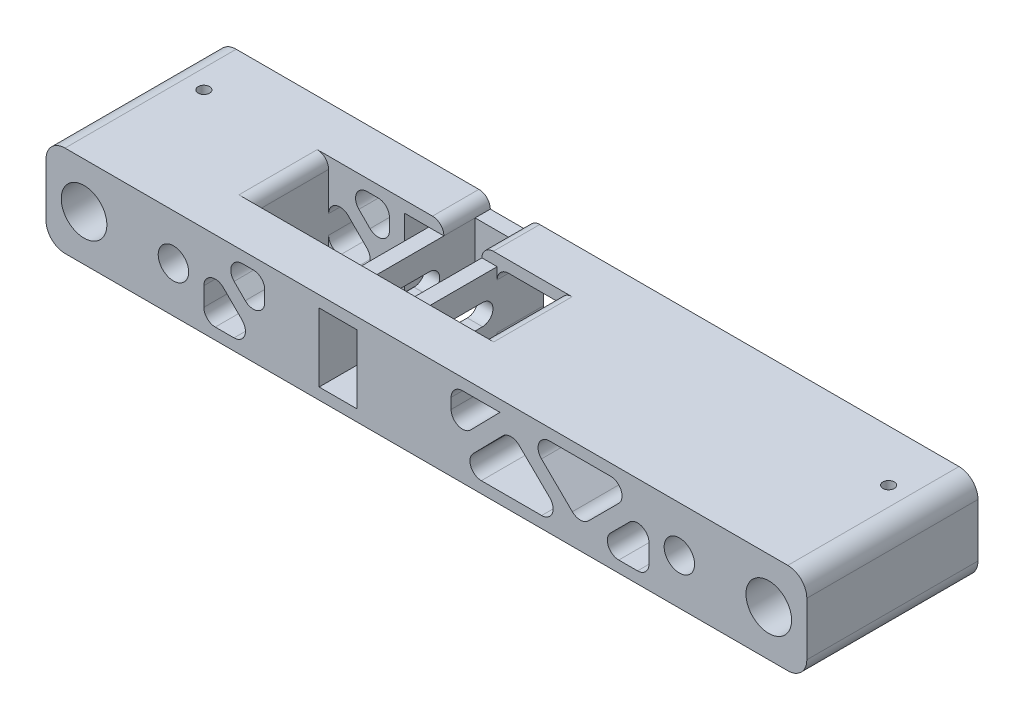
SolidWorks part; units mm, degrees
ref_plane "Front Plane" through (0, 0, 0) normal (0, 0, 1) x (1, 0, 0)
ref_plane "Top Plane" through (0, 0, 0) normal (0, 1, 0) x (1, 0, 0)
ref_plane "Right Plane" through (0, 0, 0) normal (1, 0, 0) x (0, 0, -1)
sketch "Sketch1" plane through (0, 0, 0) normal (0, 0, 1) x (1, 0, 0)
  line L0 (-58.5, 24) -> (-58.5, 0) construction
  line L1 (0, 0) -> (-100, 0)
  line L2 (0, 0) -> (0, 24)
  line L3 (0, 24) -> (-100, 24)
  line L4 (-100, 0) -> (-100, 24)
  circle A0 centre (-90, 12) radius 6
  circle A1 centre (-66.5, 12) radius 4
  point P9 (-100, 12)
  dimension "D3" = 12
  dimension "D4" = 8
  dimension "D1" = 100
  dimension "D2" = 24
  dimension "D5" = 23.5
  dimension "D6" = 10
  dimension "D7" = 8
  dimension "D8" = 41.5
extrude "Boss-Extrude1" add sketch "Sketch1" along normal blind 40
sketch "Sketch2" plane through (0, 0, 0) normal (0, 0, -1) x (-1, 0, 0)
  line L1 (100, 24) -> (0, 24)
  line L2 (100, 24) -> (100, 0)
  line L3 (100, 0) -> (0, 0)
  line L4 (0, 24) -> (0, 0)
extrude "Boss-Extrude2" add sketch "Sketch2" along normal blind 5
sketch "Sketch3" plane through (0, 24, 0) normal (0, 1, 0) x (1, 0, 0)
  line L0 (0, -40) -> (0, 5) construction
  line L1 (0, 5) -> (-58.5, 5)
  line L2 (0, 5) -> (0, -27.8)
  line L3 (0, -27.8) -> (-58.5, -27.8)
  line L4 (-58.5, 5) -> (-58.5, -27.8)
  line L5 (-100, -40) -> (-100, 5) construction
  line L7 (0, -40) -> (-100, -40) construction
  line L8 (-100, 5) -> (0, 5) construction
  dimension "D1" = 41.5
  dimension "D3" = 12.2
extrude "Cut-Extrude1" cut sketch "Sketch3" against normal up to next
mirror "Mirror2" of "Boss-Extrude2", "Cut-Extrude1", "Boss-Extrude1"
sketch "Sketch4" plane through (0, 0, 27.8) normal (0, 0, -1) x (-1, 0, 0)
  line L0 (58.5, 0) -> (58.5, 24) construction
  line L1 (28.2, 3) -> (18.2, 3)
  line L2 (28.2, 3) -> (28.2, 21)
  line L3 (28.2, 21) -> (18.2, 21)
  line L4 (18.2, 3) -> (18.2, 21)
  line L5 (28.2, 3) -> (18.2, 21) construction
  line L6 (28.2, 21) -> (18.2, 3) construction
  point P0 (23.2, 12)
  point P7 (58.5, 12)
  dimension "D1" = 30.3
  dimension "D2" = 10
  dimension "D3" = 18
extrude "Cut-Extrude2" cut sketch "Sketch4" against normal through all
sketch "Sketch5" plane through (0, 0, 27.8) normal (0, 0, -1) x (-1, 0, 0)
  line L0 (18.2, 3) -> (28.2, 3) construction
  line L1 (28.2, 21) -> (32.2, 21)
  line L2 (28.2, 21) -> (28.2, 3)
  line L3 (28.2, 3) -> (32.2, 3)
  line L4 (32.2, 21) -> (32.2, 3)
  line L5 (18.2, 21) -> (14.2, 21)
  line L6 (18.2, 21) -> (18.2, 3)
  line L7 (18.2, 3) -> (14.2, 3)
  line L8 (14.2, 21) -> (14.2, 3)
  dimension "D1" = 4
  dimension "D2" = 4
extrude "Boss-Extrude3" add sketch "Sketch5" along normal blind 28.8
sketch "Sketch6" plane through (0, 0, -1) normal (0, 0, -1) x (-1, 0, 0)
  line L1 (14.2, 21) -> (32.2, 21)
  line L2 (14.2, 21) -> (14.2, 3)
  line L3 (14.2, 3) -> (32.2, 3)
  line L4 (32.2, 21) -> (32.2, 3)
extrude "Boss-Extrude4" add sketch "Sketch6" along normal blind 4
sketch "Sketch7" plane through (-14.2, 0, 0) normal (1, 0, 0) x (0, 0, -1)
  line L0 (-20.05, 12) -> (-11.05, 12) construction
  line L1 (-20.05, 14.75) -> (-11.05, 14.75)
  line L2 (-20.05, 9.25) -> (-11.05, 9.25)
  line L3 (-27.8, 21) -> (-27.8, 3) construction
  line L4 (5, 21) -> (-27.8, 21) construction
  arc A0 (-20.05, 14.75) -> (-20.05, 9.25) centre (-20.05, 12) ccw
  arc A1 (-11.05, 9.25) -> (-11.05, 14.75) centre (-11.05, 12) ccw
  point P2 (-15.55, 12)
  point P7 (-22.8, 12)
  dimension "D1" = 9
  dimension "D2" = 5.5
  dimension "D3" = 5
  dimension "D4" = 9
extrude "Cut-Extrude3" cut sketch "Sketch7" against normal up to vertex
sketch "Sketch8" plane through (0, 21, 0) normal (0, 1, 0) x (1, 0, 0)
  line L0 (-32.2, 5) -> (-14.2, 5) construction
  line L1 (-18.2, 5) -> (58.5, 5)
  line L2 (-18.2, 5) -> (-18.2, -7.2)
  line L3 (-18.2, -7.2) -> (58.5, -7.2)
  line L4 (58.5, 5) -> (58.5, -7.2)
  line L5 (-58.5, 5) -> (-58.5, -27.8) construction
  line L6 (-28.2, 5) -> (-58.5, 5)
  line L7 (-28.2, 5) -> (-28.2, -7.2)
  line L8 (-28.2, -7.2) -> (-58.5, -7.2)
  line L9 (-58.5, 5) -> (-58.5, -7.2)
  line L10 (-28.2, 1) -> (-28.2, -27.8) construction
  line L11 (-18.2, 1) -> (-18.2, -27.8) construction
  line L12 (58.5, 5) -> (58.5, -27.8) construction
  dimension "D1" = 12.2
  dimension "D2" = 12.2
extrude "Boss-Extrude5" add sketch "Sketch8" along normal up to vertex (3 mm away)
sketch "Sketch13" plane through (58.5, 0, 0) normal (-1, 0, 0) x (0, 0, 1)
  line L0 (7.2, 24) -> (7.2, 21) construction
  line L1 (-5, 0) -> (7.2, 0)
  line L2 (-5, 0) -> (-5, 3)
  line L3 (-5, 3) -> (7.2, 3)
  line L4 (7.2, 0) -> (7.2, 3)
extrude "Boss-Extrude7" add sketch "Sketch13" along normal up to vertex
sketch "Sketch14" plane through (-58.5, 0, 0) normal (1, 0, 0) x (0, 0, -1)
  line L0 (-7.2, 24) -> (-7.2, 21) construction
  line L1 (5, 0) -> (-7.2, 0)
  line L2 (5, 0) -> (5, 3)
  line L3 (5, 3) -> (-7.2, 3)
  line L4 (-7.2, 0) -> (-7.2, 3)
extrude "Boss-Extrude8" add sketch "Sketch14" along normal up to vertex
sketch "Sketch9" plane through (0, 0, -5) normal (0, 0, -1) x (-1, 0, 0)
  line L0 (-58.5, 21) -> (-40.5, 3) construction
  line L2 (-40.5, 3) -> (-22.15, 21) construction
  line L3 (-58.5, 21) -> (14.2, 21) construction
  line L4 (-22.15, 21) -> (-4.4933, 3) construction
  line L5 (-4.4933, 3) -> (-4.4933, 21) construction
  line L6 (58.5, 21) -> (40.5, 3) construction
  line L8 (40.5, 3) -> (40.5, 21) construction
  line L9 (32.2, 21) -> (58.5, 21) construction
  line L10 (-58.5, 3) -> (-58.5, 21) construction
  line L11 (58.5, 0) -> (58.5, 24) construction
  line L12 (-58.5, 18.1716) -> (-43.3284, 3)
  line L13 (-37.6439, 3) -> (-22.1772, 18.1717)
  line L14 (-22.1772, 18.1717) -> (-7.2949, 3)
  line L15 (-2.4933, 3) -> (-2.4933, 21)
  line L16 (55.6716, 21) -> (42.5, 7.8284)
  line L17 (42.5, 7.8284) -> (42.5, 21)
  line L18 (-55.6716, 21) -> (-40.4864, 5.8149)
  line L19 (-40.4864, 5.8149) -> (-25.0061, 21)
  line L20 (-19.3484, 21) -> (-6.4933, 7.8949)
  line L21 (-6.4933, 7.8949) -> (-6.4933, 21)
  line L22 (58.5, 18.1716) -> (43.3284, 3)
  line L23 (38.5, 3) -> (38.5, 21)
  line L24 (-58.5, 18.1716) -> (-58.5, 21)
  line L25 (-58.5, 21) -> (-55.6716, 21)
  line L26 (-6.4933, 21) -> (-2.4933, 21)
  line L27 (-7.2949, 3) -> (-2.4933, 3)
  line L28 (-37.6439, 3) -> (-43.3284, 3)
  line L29 (-25.0061, 21) -> (-19.3484, 21)
  line L30 (-57.0858, 22.4142) -> (-40.4864, 5.8149) construction
  line L31 (-59.9142, 19.5858) -> (-40.5136, 0.1851) construction
  line L32 (-40.5136, 0.1851) -> (-22.1772, 18.1717) construction
  line L33 (-22.1772, 18.1717) -> (-2.4933, -1.8949) construction
  line L34 (-2.4933, -1.8949) -> (-2.4933, 21) construction
  line L35 (-22.1228, 23.8283) -> (-6.4933, 7.8949) construction
  line L36 (-40.4864, 5.8149) -> (-22.1228, 23.8283) construction
  line L37 (38.5, 21) -> (42.5, 21)
  line L38 (55.6716, 21) -> (58.5, 21)
  line L39 (58.5, 21) -> (58.5, 18.1716)
  line L40 (58.5, 3) -> (58.5, 21) construction
  line L41 (43.3284, 3) -> (38.5, 3)
  line L42 (38.5, -1.8284) -> (38.5, 21) construction
  line L43 (59.9142, 19.5858) -> (38.5, -1.8284) construction
  line L44 (57.0858, 22.4142) -> (42.5, 7.8284) construction
  line L45 (14.2, 3) -> (-58.5, 3) construction
  line L47 (32.2, 3) -> (58.5, 3) construction
  dimension "D1" = 45
  dimension "D2" = 45
  dimension "D3" = 2
  dimension "D4" = 2
extrude "Boss-Extrude6" add sketch "Sketch9" against normal up to vertex (12.2 mm away) up to point (-14.2, 21, 7.2)
sketch "Sketch11" plane through (0, 24, 0) normal (0, 1, 0) x (1, 0, 0)
  line L0 (96, 0) -> (84, 0) construction
  line L1 (-84, 0) -> (-96, 0) construction
  circle A0 centre (90, -8.5) radius 1.5
  circle A1 centre (-90, -8.5) radius 1.5
  point P12 (-90, 0)
  point P13 (90, 0)
  dimension "D3" = 3
  dimension "D4" = 3
  dimension "D1" = 8.5
  dimension "D2" = 8.5
extrude "Cut-Extrude5" cut sketch "Sketch11" against normal through all
sketch "Sketch12" plane through (0, 0, 0) normal (0, -1, 0) x (1, 0, 0)
  line L1 (-87.25, 6.9123) -> (-87.25, 10.0877)
  line L2 (-87.25, 10.0877) -> (-90, 11.6754)
  line L3 (-90, 11.6754) -> (-92.75, 10.0877)
  line L4 (-92.75, 10.0877) -> (-92.75, 6.9123)
  line L5 (-92.75, 6.9123) -> (-90, 5.3246)
  line L6 (-90, 5.3246) -> (-87.25, 6.9123)
  line L7 (92.75, 10.0877) -> (90, 11.6754)
  line L8 (90, 11.6754) -> (87.25, 10.0877)
  line L9 (87.25, 10.0877) -> (87.25, 6.9123)
  line L10 (87.25, 6.9123) -> (90, 5.3246)
  line L11 (90, 5.3246) -> (92.75, 6.9123)
  line L12 (92.75, 6.9123) -> (92.75, 10.0877)
  line L14 (-100, 40) -> (-100, -5) construction
  line L15 (100, 40) -> (100, -5) construction
  circle A0 centre (-90, 8.5) radius 2.75 construction
  circle A1 centre (90, 8.5) radius 2.75 construction
  point P22 (87.25, 8.5)
  dimension "D1" = 5.5
  dimension "D2" = 5.5
extrude "Cut-Extrude6" cut sketch "Sketch12" against normal blind 4
sketch "Sketch15" plane through (0, 0, 27.8) normal (0, 0, -1) x (-1, 0, 0)
  line L6 (-6.4933, 7.8949) -> (-19.3484, 21) construction
  line L7 (-6.4933, 21) -> (-6.4933, 7.8949) construction
  line L8 (-6.4933, 21) -> (-19.3484, 21) construction
  line L9 (-6.4933, 7.8949) -> (-19.3484, 21)
  line L10 (-6.4933, 21) -> (-6.4933, 7.8949)
  line L11 (-6.4933, 21) -> (-19.3484, 21)
  line L12 (-37.6439, 3) -> (-22.1772, 18.1717) construction
  line L39 (-58.5, 18.1716) -> (-43.3284, 3)
  line L40 (-58.5, 24) -> (-58.5, 18.1716)
  line L41 (18.2, 24) -> (-58.5, 24)
  line L42 (18.2, 21) -> (18.2, 24)
  line L43 (14.2, 21) -> (18.2, 21)
  line L44 (-2.4933, 21) -> (14.2, 21)
  line L45 (-2.4933, 3) -> (-2.4933, 21)
  line L46 (14.2, 3) -> (-2.4933, 3)
  line L47 (18.2, 3) -> (14.2, 3)
  line L48 (18.2, 0) -> (18.2, 3)
  line L49 (-58.5, 0) -> (18.2, 0)
  line L50 (-58.5, 3) -> (-58.5, 0)
  line L51 (-43.3284, 3) -> (-58.5, 3)
  line L52 (-58.5, 18.1716) -> (-43.3284, 3)
  line L53 (-58.5, 24) -> (-58.5, 18.1716)
  line L54 (-2.4933, 24) -> (-58.5, 24)
  line L62 (-58.5, 0) -> (-2.4933, 0)
  line L63 (-58.5, 3) -> (-58.5, 0)
  line L64 (-43.3284, 3) -> (-58.5, 3)
  line L65 (-7.2949, 3) -> (-37.6439, 3) construction
  line L66 (-22.1772, 18.1717) -> (-7.2949, 3) construction
  line L67 (-37.6439, 3) -> (-22.1772, 18.1717)
  line L68 (-7.2949, 3) -> (-37.6439, 3)
  line L69 (-22.1772, 18.1717) -> (-7.2949, 3)
  line L70 (-25.0061, 21) -> (-55.6716, 21) construction
  line L71 (-25.0061, 21) -> (-40.4864, 5.8149) construction
  line L72 (-40.4864, 5.8149) -> (-55.6716, 21) construction
  line L73 (-25.0061, 21) -> (-55.6716, 21)
  line L74 (-25.0061, 21) -> (-40.4864, 5.8149)
  line L75 (-40.4864, 5.8149) -> (-55.6716, 21)
  line L83 (-2.4933, 0) -> (-2.4933, 24)
  dimension "D3" = 56.0067
  dimension "D2" = 0
extrude "Boss-Extrude9" add sketch "Sketch15" along normal up to vertex (20.6 mm away)
sketch "Sketch17" plane through (2.4933, 0, 0) normal (-1, 0, 0) x (0, 0, 1)
  line L0 (27.8, 0) -> (27.8, 24) construction
  line L1 (7.2, 21) -> (27.8, 21)
  line L2 (7.2, 21) -> (7.2, 7.8949)
  line L3 (7.2, 7.8949) -> (27.8, 7.8949)
  line L4 (27.8, 21) -> (27.8, 7.8949)
extrude "Cut-Extrude8" cut sketch "Sketch17" against normal up to vertex (16.8551 mm away) up to point (19.3484, 21, -5)
fillet "Fillet3" radius 5 4 edges at (100, 0, 17.5) (100, 24, 17.5) (-100, 24, 17.5) (-100, 0, 17.5)
sketch "Sketch18" plane through (0, 0, 27.8) normal (0, 0, -1) x (-1, 0, 0)
  line L0 (-6.4933, 21) -> (-6.4933, 7.8949) construction
  line L1 (-19.3484, 21) -> (-6.4933, 21) construction
  line L2 (-6.4933, 7.8949) -> (-19.3484, 21) construction
  line L3 (-7.2949, 3) -> (-37.6439, 3) construction
  line L4 (-22.1772, 18.1717) -> (-7.2949, 3) construction
  line L5 (-37.6439, 3) -> (-22.1772, 18.1717) construction
  line L6 (-25.0061, 21) -> (-40.4864, 5.8149) construction
  line L7 (-55.6716, 21) -> (-25.0061, 21) construction
  line L8 (-40.4864, 5.8149) -> (-55.6716, 21) construction
  line L9 (-58.5, 18.1716) -> (-43.3284, 3) construction
  line L10 (-43.3284, 3) -> (-58.5, 3) construction
  line L11 (-58.5, 3) -> (-58.5, 18.1716) construction
  line L12 (-6.4933, 21) -> (-6.4933, 7.8949)
  line L13 (-19.3484, 21) -> (-6.4933, 21)
  line L14 (-6.4933, 7.8949) -> (-19.3484, 21)
  line L15 (-7.2949, 3) -> (-37.6439, 3)
  line L16 (-22.1772, 18.1717) -> (-7.2949, 3)
  line L17 (-37.6439, 3) -> (-22.1772, 18.1717)
  line L18 (-25.0061, 21) -> (-40.4864, 5.8149)
  line L19 (-55.6716, 21) -> (-25.0061, 21)
  line L20 (-40.4864, 5.8149) -> (-55.6716, 21)
  line L21 (-58.5, 18.1716) -> (-43.3284, 3)
  line L22 (-43.3284, 3) -> (-58.5, 3)
  line L23 (-58.5, 3) -> (-58.5, 18.1716)
  line L24 (43.3284, 3) -> (58.5, 3) construction
  line L25 (58.5, 3) -> (58.5, 18.1716) construction
  line L26 (43.3284, 3) -> (58.5, 18.1716) construction
  line L27 (42.5, 21) -> (55.6716, 21) construction
  line L28 (55.6716, 21) -> (42.5, 7.8284) construction
  line L29 (42.5, 7.8284) -> (42.5, 21) construction
  line L30 (43.3284, 3) -> (58.5, 3)
  line L31 (58.5, 3) -> (58.5, 18.1716)
  line L32 (43.3284, 3) -> (58.5, 18.1716)
  line L33 (42.5, 21) -> (55.6716, 21)
  line L34 (55.6716, 21) -> (42.5, 7.8284)
  line L35 (42.5, 7.8284) -> (42.5, 21)
extrude "Cut-Extrude9" cut sketch "Sketch18" against normal up to next
fillet "Fillet5" radius 3 41 edges at (-14.2, 21, 1.1) (-14.2, 3, 1.1) (-18.2, 22.5, -5) (-18.2, 22.5, 7.2) (-18.2, 24, 1.1) (-58.5, 24, 17.5) (-28.2, 22.5, 7.2) (-28.2, 22.5, -5) (-28.2, 24, 1.1) (58.5, 3, 17.5) (-28.2, 1.5, -5) (-28.2, 1.5, 7.2) (-28.2, 0, 1.1) (55.6716, 21, 17.5) (40.4864, 5.8149, 17.5) (25.0061, 21, 17.5) (7.2949, 3, 17.5) (22.1772, 18.1717, 17.5) (37.6439, 3, 17.5) (43.3284, 3, 17.5) (58.5, 18.1716, 17.5) (-58.5, 18.1716, 1.1) (-43.3284, 3, 1.1) (-42.5, 21, 1.1) (-42.5, 7.8284, 1.1) (-55.6716, 21, 1.1) (2.4933, 1.5, 7.2) (2.4933, 22.5, 7.2) (2.4933, 0, 17.5) (2.4933, 24, 17.5) (-58.5, 0, 17.5) (6.4933, 21, 1.1) (6.4933, 7.8949, 1.1) (12.0965, 7.8949, 17.5) (-43.3284, 3, 33.9) (-58.5, 18.1716, 33.9) (-42.5, 7.8284, 33.9) (-42.5, 21, 33.9) (-55.6716, 21, 33.9) (6.4933, 21, 33.9) (6.4933, 7.8949, 33.9)
